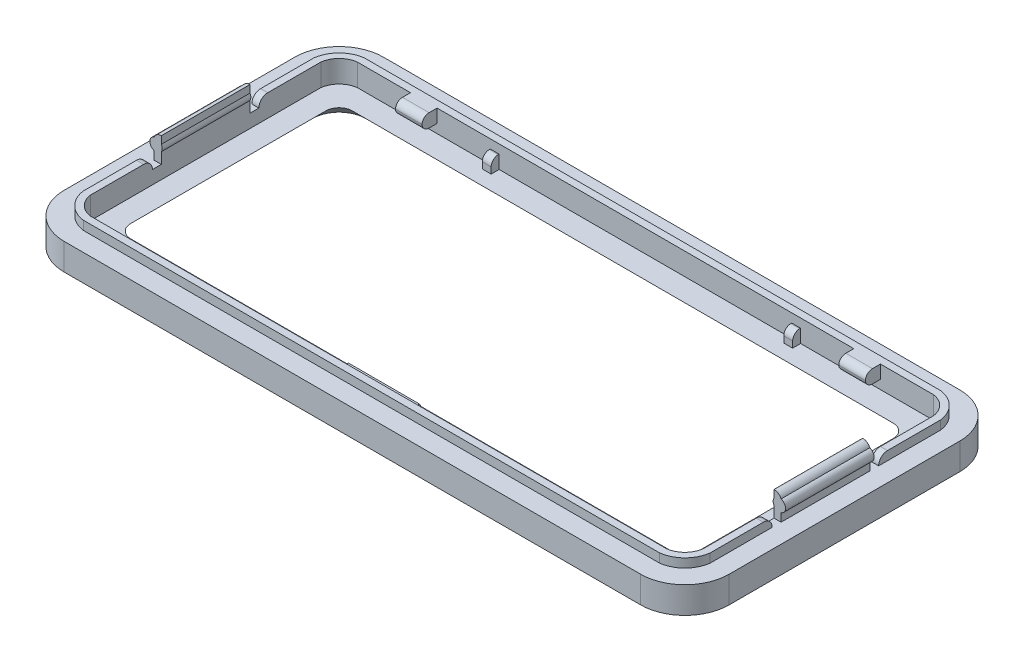
SolidWorks part; units mm, degrees
ref_plane "前视基准面" through (0, 0, 0) normal (0, 0, 1) x (1, 0, 0)
ref_plane "上视基准面" through (0, 0, 0) normal (0, 1, 0) x (1, 0, 0)
ref_plane "右视基准面" through (0, 0, 0) normal (1, 0, 0) x (0, 0, -1)
sketch "zero" plane through (0, 0, 0) normal (0, 1, 0) x (1, 0, 0)
  line L1 (-29.5, 15) -> (29.5, 15)
  line L2 (-32.5, 12) -> (-32.5, -12)
  line L3 (-29.5, -15) -> (29.5, -15)
  line L4 (32.5, 12) -> (32.5, -12)
  line L5 (-32.5, 15) -> (32.5, -15) construction
  line L6 (-32.5, -15) -> (32.5, 15) construction
  line L7 (-25.7, -15) -> (-14.5, -15)
  line L8 (-25.7, -15) -> (-25.7, -9.6569)
  line L9 (-25.7, -9.6569) -> (-14.5, -9.6569)
  line L10 (-14.5, -15) -> (-14.5, -9.6569)
  line L11 (5.2, -15) -> (12.7, -15)
  line L12 (5.2, -15) -> (5.2, -11)
  line L13 (5.2, -11) -> (12.7, -11)
  line L14 (12.7, -15) -> (12.7, -11)
  line L15 (17.8, -15) -> (25.3, -15)
  line L16 (17.8, -15) -> (17.8, -11)
  line L17 (17.8, -11) -> (25.3, -11)
  line L18 (25.3, -15) -> (25.3, -11)
  line L19 (-32.5, 7.7) -> (-19.5, 7.7)
  line L20 (-32.5, 7.7) -> (-32.5, -4.3)
  line L21 (-32.5, -4.3) -> (-19.5, -4.3)
  line L22 (-19.5, 7.7) -> (-19.5, -4.3)
  line L23 (-25.5, 14) -> (25.5, 14)
  line L24 (-25.5, 14) -> (-25.5, 8.8)
  line L25 (-25.5, 8.8) -> (25.5, 8.8)
  line L26 (25.5, 14) -> (25.5, 8.8)
  line L27 (-19.5, 7.2329) -> (-35.5, 7.2329)
  line L28 (-19.5, 7.2329) -> (-19.5, -3.7671)
  line L29 (-19.5, -3.7671) -> (-35.5, -3.7671)
  line L30 (-35.5, 7.2329) -> (-35.5, -3.7671)
  arc A0 (29.5, -15) -> (32.5, -12) centre (29.5, -12) ccw
  arc A1 (29.5, 15) -> (32.5, 12) centre (29.5, 12) cw
  arc A2 (-32.5, -12) -> (-29.5, -15) centre (-29.5, -12) ccw
  arc A3 (-29.5, 15) -> (-32.5, 12) centre (-29.5, 12) ccw
  circle A4 centre (-29, 11.4) radius 3
  circle A5 centre (-29, -11.5) radius 3
  circle A6 centre (29, 11.4) radius 3
  circle A7 centre (29, -11.5) radius 3
  circle A8 centre (-29, 11.4) radius 1.375
  circle A9 centre (-29, -11.5) radius 1.375
  circle A10 centre (29, -11.5) radius 1.375
  circle A11 centre (29, 11.4) radius 1.375
  point P0 (0, 0)
  dimension "D3" = 3
  dimension "D4" = 6
  dimension "D9" = 2.75
  dimension "D1" = 65
  dimension "D2" = 30
  dimension "D5" = 3.6
  dimension "D6" = 3.5
  dimension "D7" = 3.5
  dimension "D8" = 3.5
  dimension "D10" = 12
  dimension "D11" = 7.3
  dimension "D12" = 13
  dimension "D13" = 11.2
  dimension "D14" = 6.8
  dimension "D15" = 19.7
  dimension "D16" = 7.5
  dimension "D17" = 7.5
  dimension "D18" = 5.1
  dimension "D19" = 4
  dimension "D20" = 5.2
  dimension "D21" = 7
  dimension "D22" = 7
  dimension "D23" = 1
  dimension "D24" = 11
  dimension "D25" = 16
sketch "sugar" plane through (0, 0, 0) normal (0, 1, 0) x (1, 0, 0)
  line L1 (-29.5, 15) -> (29.5, 15)
  line L2 (-32.5, 12) -> (-32.5, -12)
  line L3 (-29.5, -15) -> (29.5, -15)
  line L4 (32.5, 12) -> (32.5, -12)
  line L5 (-32.5, 15) -> (32.5, -15) construction
  line L6 (-32.5, -15) -> (32.5, 15) construction
  line L7 (23.5, -11.5) -> (19.5, -11.5)
  line L8 (23.5, -11.5) -> (23.5, -13.9082)
  line L9 (23.5, -13.9082) -> (19.5, -13.9082)
  line L10 (19.5, -11.5) -> (19.5, -13.9082)
  line L11 (16, -11.0071) -> (8.5, -11.0071)
  line L12 (16, -11.0071) -> (16, -15)
  line L13 (16, -15) -> (8.5, -15)
  line L14 (8.5, -11.0071) -> (8.5, -15)
  line L15 (20.5, -13.9082) -> (22.5, -13.9082)
  line L16 (20.5, -13.9082) -> (20.5, -14.8173)
  line L17 (20.5, -14.8173) -> (22.5, -14.8173)
  line L18 (22.5, -13.9082) -> (22.5, -14.8173)
  arc A0 (29.5, 15) -> (32.5, 12) centre (29.5, 12) cw
  arc A1 (29.5, -15) -> (32.5, -12) centre (29.5, -12) ccw
  arc A2 (-32.5, -12) -> (-29.5, -15) centre (-29.5, -12) ccw
  arc A3 (-29.5, 15) -> (-32.5, 12) centre (-29.5, 12) ccw
  circle A4 centre (-29, 11.4) radius 3
  circle A5 centre (-29, 11.4) radius 1.375
  circle A6 centre (-29, -11.5) radius 3
  circle A7 centre (-29, -11.5) radius 1.375
  circle A8 centre (29, 11.4) radius 3
  circle A9 centre (29, 11.4) radius 1.375
  circle A10 centre (29, -11.5) radius 3
  circle A11 centre (29, -11.5) radius 1.375
  dimension "D3" = 3
  dimension "D1" = 65
  dimension "D2" = 30
  dimension "D4" = 9
  dimension "D5" = 4
  dimension "D6" = 3.5
  dimension "D7" = 7.5
  dimension "D8" = 2
  dimension "D9" = 1
sketch "case" plane through (0, 0, 0) normal (0, 1, 0) x (1, 0, 0)
  line L1 (-34.0422, 18) -> (30.9578, 18)
  line L2 (-39.0422, 13) -> (-39.0422, -13)
  line L3 (-34.0422, -18) -> (30.9578, -18)
  line L4 (35.9578, 13) -> (35.9578, -13)
  line L5 (-39.0422, 18) -> (35.9578, -18) construction
  line L6 (-39.0422, -18) -> (35.9578, 18) construction
  arc A0 (-39.0422, -13) -> (-34.0422, -18) centre (-34.0422, -13) ccw
  arc A1 (30.9578, -18) -> (35.9578, -13) centre (30.9578, -13) ccw
  arc A2 (30.9578, 18) -> (35.9578, 13) centre (30.9578, 13) cw
  arc A3 (-34.0422, 18) -> (-39.0422, 13) centre (-34.0422, 13) ccw
  point P0 (-1.5422, 0)
  point P3 (-1.5422, 0)
  dimension "D3" = 5
  dimension "D1" = 75
  dimension "D2" = 36
extrude "凸台-拉伸2" add sketch "case" along normal blind 3
sketch "草图2" plane through (0, 0, 0) normal (0, 1, 0) x (1, 0, 0)
  line L4 (-34.0422, -15.05) -> (30.9578, -15.05)
  line L5 (33.0078, -13) -> (33.0078, 13)
  line L6 (30.9578, 15.05) -> (-34.0422, 15.05)
  line L7 (-36.0922, 13) -> (-36.0922, -13)
  line L12 (33.8078, -13) -> (33.8078, 13)
  line L13 (30.9578, 15.85) -> (-34.0422, 15.85)
  line L14 (-36.8922, 13) -> (-36.8922, -13)
  line L15 (-34.0422, -15.85) -> (30.9578, -15.85)
  arc A4 (30.9578, -15.05) -> (33.0078, -13) centre (30.6303, -12.6725) ccw
  arc A5 (33.0078, 13) -> (30.9578, 15.05) centre (30.6303, 12.6725) ccw
  arc A6 (-34.0422, 15.05) -> (-36.0922, 13) centre (-33.7147, 12.6725) ccw
  arc A7 (-36.0922, -13) -> (-34.0422, -15.05) centre (-33.7147, -12.6725) ccw
  arc A12 (30.9578, -15.85) -> (33.8078, -13) centre (30.535, -12.5772) ccw
  arc A13 (33.8078, 13) -> (30.9578, 15.85) centre (30.535, 12.5772) ccw
  arc A14 (-34.0422, 15.85) -> (-36.8922, 13) centre (-33.6194, 12.5772) ccw
  arc A15 (-36.8922, -13) -> (-34.0422, -15.85) centre (-33.6194, -12.5772) ccw
ref_plane "基准面1" through (0, 3, 0) normal (0, 1, 0) x (1, 0, 0)
sketch "草图3" plane through (0, 3, 0) normal (0, 1, 0) x (1, 0, 0)
  line L4 (-34.0422, -15.05) -> (30.9578, -15.05)
  line L5 (33.0078, -13) -> (33.0078, 13)
  line L6 (30.9578, 15.05) -> (-34.0422, 15.05)
  line L7 (-36.0922, 13) -> (-36.0922, -13)
  line L8 (-34.0422, -15.05) -> (30.9578, -15.05)
  line L9 (33.0078, -13) -> (33.0078, 13)
  line L10 (30.9578, 15.05) -> (-34.0422, 15.05)
  line L11 (-36.0922, 13) -> (-36.0922, -13)
  line L12 (-36.8922, 13) -> (-36.8922, -13)
  line L13 (-34.0422, -15.85) -> (30.9578, -15.85)
  line L14 (33.8078, -13) -> (33.8078, 13)
  line L15 (30.9578, 15.85) -> (-34.0422, 15.85)
  line L16 (-36.8922, 13) -> (-36.8922, -13)
  line L17 (-34.0422, -15.85) -> (30.9578, -15.85)
  line L18 (33.8078, -13) -> (33.8078, 13)
  line L19 (30.9578, 15.85) -> (-34.0422, 15.85)
  arc A4 (30.9578, -15.05) -> (33.0078, -13) centre (30.6303, -12.6725) ccw
  arc A5 (33.0078, 13) -> (30.9578, 15.05) centre (30.6303, 12.6725) ccw
  arc A6 (-34.0422, 15.05) -> (-36.0922, 13) centre (-33.7147, 12.6725) ccw
  arc A7 (-36.0922, -13) -> (-34.0422, -15.05) centre (-33.7147, -12.6725) ccw
  arc A8 (30.9578, -15.05) -> (33.0078, -13) centre (30.6303, -12.6725) ccw
  arc A9 (33.0078, 13) -> (30.9578, 15.05) centre (30.6303, 12.6725) ccw
  arc A10 (-34.0422, 15.05) -> (-36.0922, 13) centre (-33.7147, 12.6725) ccw
  arc A11 (-36.0922, -13) -> (-34.0422, -15.05) centre (-33.7147, -12.6725) ccw
  arc A12 (-36.8922, -13) -> (-34.0422, -15.85) centre (-33.6194, -12.5772) ccw
  arc A13 (30.9578, -15.85) -> (33.8078, -13) centre (30.535, -12.5772) ccw
  arc A14 (33.8078, 13) -> (30.9578, 15.85) centre (30.535, 12.5772) ccw
  arc A15 (-34.0422, 15.85) -> (-36.8922, 13) centre (-33.6194, 12.5772) ccw
  arc A16 (-36.8922, -13) -> (-34.0422, -15.85) centre (-33.6194, -12.5772) ccw
  arc A17 (30.9578, -15.85) -> (33.8078, -13) centre (30.535, -12.5772) ccw
  arc A18 (33.8078, 13) -> (30.9578, 15.85) centre (30.535, 12.5772) ccw
  arc A19 (-34.0422, 15.85) -> (-36.8922, 13) centre (-33.6194, 12.5772) ccw
  dimension "D1" = 0
  dimension "D2" = 0
extrude "凸台-拉伸4" add sketch "草图3" along normal blind 1
ref_plane "基准面3" through (33.8078, 0, 0) normal (1, 0, 0) x (0, 0, -1)
sketch "草图7" plane through (0, 3, 0) normal (0, 1, 0) x (1, 0, 0)
  line L0 (-36.8922, 13) -> (-36.8922, -13) construction
  line L1 (-36.8922, 5) -> (-36.0922, 5)
  line L2 (-36.8922, 5) -> (-36.8922, -5)
  line L3 (-36.8922, -5) -> (-36.0922, -5)
  line L4 (-36.0922, 5) -> (-36.0922, -5)
  line L5 (-36.0922, 13) -> (-36.0922, -13) construction
  point P10 (-36.0922, 0)
  dimension "D1" = 5
  dimension "D2" = 10
extrude "凸台-拉伸8" add sketch "草图7" along normal blind 2.8
ref_plane "基准面5" through (0, 0, 5) normal (0, 0, 1) x (1, 0, 0)
sketch "草图8" plane through (0, 0, 5) normal (0, 0, 1) x (1, 0, 0)
  line L0 (-34.0422, 3) -> (-39.0422, 3) construction
  line L1 (-36.8922, 5.8) -> (-36.8922, 4) construction
  circle A0 centre (-36.6922, 4.6) radius 0.7
  dimension "D1" = 1.4
  dimension "D2" = 1.6
  dimension "D3" = 0.2
extrude "凸台-拉伸9" add sketch "草图8" against normal blind 10
fillet "圆角1" radius 0.85 1 edges at (-36.8922, 5.8, 0)
ref_plane "基准面7" through (-36.8922, 0, 0) normal (-1, 0, 0) x (0, 0, 1)
sketch "草图11" plane through (-36.8922, 0, 0) normal (-1, 0, 0) x (0, 0, 1)
  line L0 (-13, 3) -> (13, 3) construction
  line L1 (5, 4) -> (6, 4)
  line L2 (5, 4) -> (5, 3)
  line L3 (5, 3) -> (6, 3)
  line L4 (6, 4) -> (6, 3)
  line L6 (-5, 4) -> (-6, 4)
  line L7 (-5, 4) -> (-5, 3)
  line L8 (-5, 3) -> (-6, 3)
  line L9 (-6, 4) -> (-6, 3)
  dimension "D1" = 1
  dimension "D2" = 1
extrude "切除-拉伸1" cut sketch "草图11" against normal blind 1.2
fillet "圆角2" radius 1 2 edges at (-36.4922, 4, 6) (-36.4922, 4, -6)
ref_plane "基准面8" through (0, 0, 0) normal (0, -1, 0) x (-1, 0, 0)
sketch "草图13" plane through (0, 4, 0) normal (0, 1, 0) x (1, 0, 0)
  line L0 (33.0078, -13) -> (33.0078, 13) construction
  line L1 (33.0078, 5) -> (33.8078, 5)
  line L2 (33.0078, 5) -> (33.0078, -5)
  line L3 (33.0078, -5) -> (33.8078, -5)
  line L4 (33.8078, 5) -> (33.8078, -5)
  line L5 (33.8078, -13) -> (33.8078, 13) construction
  line L7 (35.9578, -13) -> (35.9578, 13) construction
  point P12 (35.9578, 0)
  point P13 (33.8078, 0)
  dimension "D1" = 10
extrude "凸台-拉伸10" add sketch "草图13" along normal blind 1.8
sketch "草图14" plane through (0, 0, 5) normal (0, 0, 1) x (1, 0, 0)
  line L0 (33.8078, 3) -> (30.9578, 3) construction
  line L1 (33.8078, 5.8) -> (33.8078, 4) construction
  circle A0 centre (33.6078, 4.6) radius 0.7
  dimension "D2" = 1.4
  dimension "D1" = 1.6
  dimension "D3" = 0.2
extrude "凸台-拉伸11" add sketch "草图14" against normal blind 10
fillet "圆角3" radius 0.85 1 edges at (33.8078, 5.8, 0)
sketch "草图15" plane through (0, 4, 0) normal (0, 1, 0) x (1, 0, 0)
  line L0 (33.8078, 5) -> (33.8078, 13) construction
  line L1 (33.0078, 5) -> (33.8078, 5)
  line L2 (33.0078, 5) -> (33.0078, 6)
  line L3 (33.0078, 6) -> (33.8078, 6)
  line L4 (33.8078, 5) -> (33.8078, 6)
  line L5 (33.8078, -13) -> (33.8078, -5) construction
  line L6 (33.0078, -5) -> (33.8078, -5)
  line L7 (33.0078, -5) -> (33.0078, -6)
  line L8 (33.0078, -6) -> (33.8078, -6)
  line L9 (33.8078, -5) -> (33.8078, -6)
  dimension "D1" = 1
  dimension "D2" = 1
extrude "切除-拉伸3" cut sketch "草图15" against normal blind 1
fillet "圆角4" radius 1 2 edges at (33.4078, 4, 6) (33.4078, 4, -6)
sketch "草图16" plane through (0, 3, 0) normal (0, 1, 0) x (1, 0, 0)
  line L4 (-34.0422, -15.05) -> (30.9578, -15.05)
  line L5 (33.0078, -13) -> (33.0078, 13)
  line L6 (30.9578, 15.05) -> (-34.0422, 15.05)
  line L7 (-36.0922, 13) -> (-36.0922, -13)
  line L8 (-34.0422, -15.05) -> (30.9578, -15.05)
  line L9 (33.0078, -13) -> (33.0078, 13)
  line L10 (30.9578, 15.05) -> (-34.0422, 15.05)
  line L11 (-36.0922, 13) -> (-36.0922, -13)
  arc A4 (30.9578, -15.05) -> (33.0078, -13) centre (30.6303, -12.6725) ccw
  arc A5 (33.0078, 13) -> (30.9578, 15.05) centre (30.6303, 12.6725) ccw
  arc A6 (-34.0422, 15.05) -> (-36.0922, 13) centre (-33.7147, 12.6725) ccw
  arc A7 (-36.0922, -13) -> (-34.0422, -15.05) centre (-33.7147, -12.6725) ccw
  arc A8 (30.9578, -15.05) -> (33.0078, -13) centre (30.6303, -12.6725) ccw
  arc A9 (33.0078, 13) -> (30.9578, 15.05) centre (30.6303, 12.6725) ccw
  arc A10 (-34.0422, 15.05) -> (-36.0922, 13) centre (-33.7147, 12.6725) ccw
  arc A11 (-36.0922, -13) -> (-34.0422, -15.05) centre (-33.7147, -12.6725) ccw
  dimension "D1" = 0
extrude "切除-拉伸4" cut sketch "草图16" against normal blind 1.5
sketch "草图17" plane through (0, 1.5, 0) normal (0, 1, 0) x (1, 0, 0)
  line L0 (30.9578, 18) -> (-34.0422, 18) construction
  line L1 (-33.5422, 12.5) -> (30.4578, 12.5)
  line L2 (-33.5422, 12.5) -> (-33.5422, -12.5)
  line L3 (-33.5422, -12.5) -> (30.4578, -12.5)
  line L4 (30.4578, 12.5) -> (30.4578, -12.5)
  line L5 (-39.0422, 13) -> (-39.0422, -13) construction
  point P4 (-1.5422, 12.5)
  point P7 (-1.5422, 18)
  point P8 (-33.5422, 0)
  point P11 (-39.0422, 0)
  dimension "D1" = 25
  dimension "D2" = 64
extrude "切除-拉伸5" cut sketch "草图17" against normal blind 1.5
fillet "圆角5" radius 1.5 4 edges at (30.4578, 0.75, 12.5) (30.4578, 0.75, -12.5) (-33.5422, 0.75, -12.5) (-33.5422, 0.75, 12.5)
sketch "草图18" plane through (0, 0, -15.05) normal (0, 0, 1) x (1, 0, 0)
  line L0 (30.9578, 4) -> (-34.0422, 4) construction
  line L1 (-28.0422, 4) -> (-25.0422, 4)
  line L2 (-28.0422, 4) -> (-28.0422, 2.5)
  line L3 (-28.0422, 2.5) -> (-25.0422, 2.5)
  line L4 (-25.0422, 4) -> (-25.0422, 2.5)
  line L8 (24.9578, 4) -> (21.9578, 4)
  line L9 (24.9578, 4) -> (24.9578, 2.5)
  line L10 (24.9578, 2.5) -> (21.9578, 2.5)
  line L11 (21.9578, 4) -> (21.9578, 2.5)
  dimension "D1" = 3
  dimension "D2" = 1.5
  dimension "D3" = 0
  dimension "D4" = 6
  dimension "D5" = 3
  dimension "D6" = 1.5
  dimension "D7" = 6
extrude "凸台-拉伸12" add sketch "草图18" along normal blind 1.7
fillet "圆角7" radius 0.8 4 edges at (23.4578, 2.5, -13.35) (23.4578, 4, -13.35) (-26.5422, 4, -13.35) (-26.5422, 2.5, -13.35)
sketch "草图19" plane through (0, 0, 15.05) normal (0, 0, -1) x (-1, 0, 0)
  line L1 (-2.4578, 3.6) -> (5.5422, 3.6)
  line L2 (-2.4578, 3.6) -> (-2.4578, 2.6)
  line L3 (-2.4578, 2.6) -> (5.5422, 2.6)
  line L4 (5.5422, 3.6) -> (5.5422, 2.6)
  line L6 (34.0422, 4) -> (-30.9578, 4) construction
  point P9 (1.5422, 3.6)
  point P10 (1.5422, 4)
  dimension "D1" = 1
  dimension "D2" = 8
  dimension "D3" = 0.4
extrude "凸台-拉伸13" add sketch "草图19" along normal blind 1.6
chamfer "倒角2" distance 1 angle 59.168 1 edges at (-1.5422, 3.6, 13.45) first distance on face at (-1.5422, 3.6, 14.25)
sketch "草图20" plane through (0, 1.5, 0) normal (0, 1, 0) x (1, 0, 0)
  line L0 (21.9578, 15.05) -> (-25.0422, 15.05) construction
  line L1 (-19.0422, 15.05) -> (-18.0422, 15.05)
  line L2 (-19.0422, 15.05) -> (-19.0422, 14.15)
  line L3 (-19.0422, 14.15) -> (-18.0422, 14.15)
  line L4 (-18.0422, 15.05) -> (-18.0422, 14.15)
  line L6 (-34.0422, -15.05) -> (30.9578, -15.05) construction
  line L7 (15.9578, 15.05) -> (14.9578, 15.05)
  line L8 (15.9578, 15.05) -> (15.9578, 14.15)
  line L9 (15.9578, 14.15) -> (14.9578, 14.15)
  line L10 (14.9578, 15.05) -> (14.9578, 14.15)
  line L11 (-19.0422, -15.05) -> (-18.0422, -15.05)
  line L12 (-19.0422, -15.05) -> (-19.0422, -14.15)
  line L13 (-19.0422, -14.15) -> (-18.0422, -14.15)
  line L14 (-18.0422, -15.05) -> (-18.0422, -14.15)
  line L15 (-39.0422, 13) -> (-39.0422, -13) construction
  line L16 (14.9578, -15.05) -> (15.9578, -15.05)
  line L17 (14.9578, -15.05) -> (14.9578, -14.15)
  line L18 (14.9578, -14.15) -> (15.9578, -14.15)
  line L19 (15.9578, -15.05) -> (15.9578, -14.15)
  line L21 (35.9578, -13) -> (35.9578, 13) construction
  dimension "D1" = 20
  dimension "D2" = 20
  dimension "D3" = 1
  dimension "D4" = 1
  dimension "D5" = 20
  dimension "D6" = 20
  dimension "D7" = 1
  dimension "D8" = 1
  dimension "D9" = 0.9
  dimension "D10" = 0.9
  dimension "D11" = 0.9
  dimension "D12" = 0.9
extrude "凸台-拉伸14" add sketch "草图20" along normal blind 1.5
fillet "圆角8" radius 0.8 4 edges at (15.4578, 3, 14.15) (-18.5422, 3, 14.15) (15.4578, 3, -14.15) (-18.5422, 3, -14.15)
chamfer "倒角3" distance 1.5 angle 45 8 edges at (-1.5422, 0, -12.5) (-33.1029, 0, -12.0607) (30.0185, 0, -12.0607) (-33.5422, 0, 0) (30.4578, 0, 0) (-33.1029, 0, 12.0607) (30.0185, 0, 12.0607) (-1.5422, 0, 12.5)
